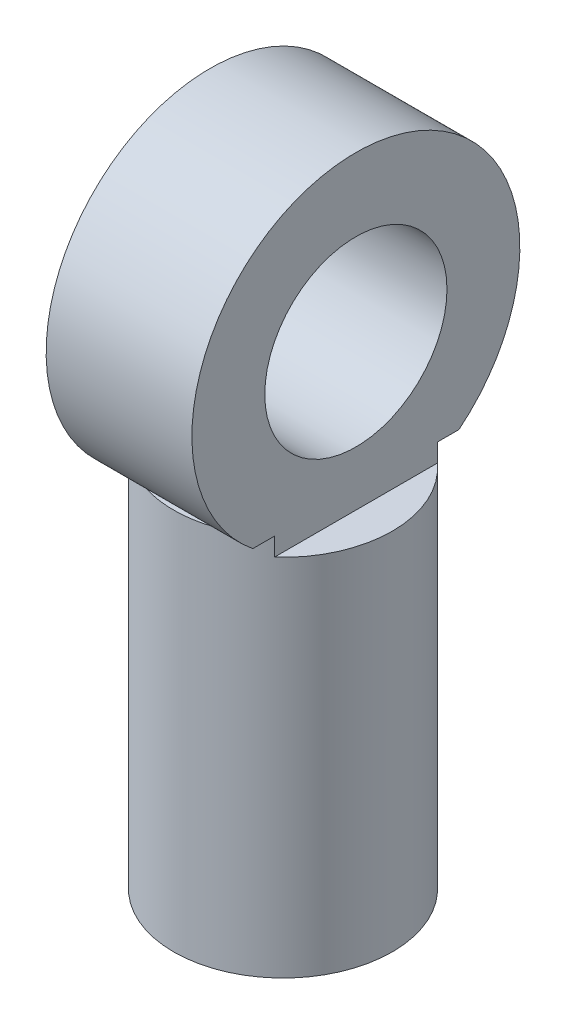
SolidWorks part; units mm, degrees
ref_plane "Front Plane" through (0, 0, 0) normal (0, 0, 1) x (1, 0, 0)
ref_plane "Top Plane" through (0, 0, 0) normal (0, 1, 0) x (1, 0, 0)
ref_plane "Right Plane" through (0, 0, 0) normal (1, 0, 0) x (0, 0, -1)
sketch "Sketch1" plane through (0, 0, 0) normal (0, 1, 0) x (1, 0, 0)
  circle A0 centre (0, 0) radius 3
  dimension "D1" = 6
extrude "crank_body" add sketch "Sketch1" along normal blind 10
sketch "Sketch2" plane through (0, 0, 0) normal (0, -1, 0) x (1, 0, 0)
  circle A0 centre (0, 0) radius 1.55
  dimension "D1" = 3.1
extrude "dowel_shaft" cut sketch "Sketch2" against normal blind 9
sketch "Sketch3" plane through (0, 0, 0) normal (1, 0, 0) x (0, 0, -1)
  line L0 (3, 10) -> (-3, 10) construction
  line L1 (-3, 10) -> (-3, 0) construction
  line L2 (-3, 10) -> (3, 10)
  line L3 (-3, 10) -> (-3, 10.5)
  line L4 (-3, 10.5) -> (3, 10.5)
  line L5 (3, 10) -> (3, 10.5)
  line L6 (3, 0) -> (3, 10) construction
  line L7 (-3, 10) -> (-3, 0) construction
  circle A0 centre (0, 14) radius 4.5
  dimension "D1" = 9
  dimension "D2" = 4
  dimension "D6" = 3
  dimension "D3" = 0.5
  dimension "D4" = 0
  dimension "D5" = 0
extrude "pin_shaft_body" add sketch "Sketch3" along normal blind 2 and the other way blind 2 contours A0 L3 L2 | L3 A0 L5 L4 | L5 A0 L3 L4 | L5 L4 L3 L2 region at (0, 10.1897, 2.6907) region at (0, 10.2628, 0) region at (0, 14.2525, 0)
sketch "Sketch4" plane through (2, 0, 0) normal (1, 0, 0) x (0, 0, -1)
  circle A0 centre (0, 14) radius 2.5
  dimension "D1" = 5
extrude "pin_shaft" cut sketch "Sketch4" against normal through all
extrude "smoothing_cuts" cut sketch "Sketch1<2>" along normal blind 10.5 flip side to cut
sketch "Sketch1<2>" plane through (0, 0, 0) normal (0, 1, 0) x (1, 0, 0) same geometry as "Sketch1"
